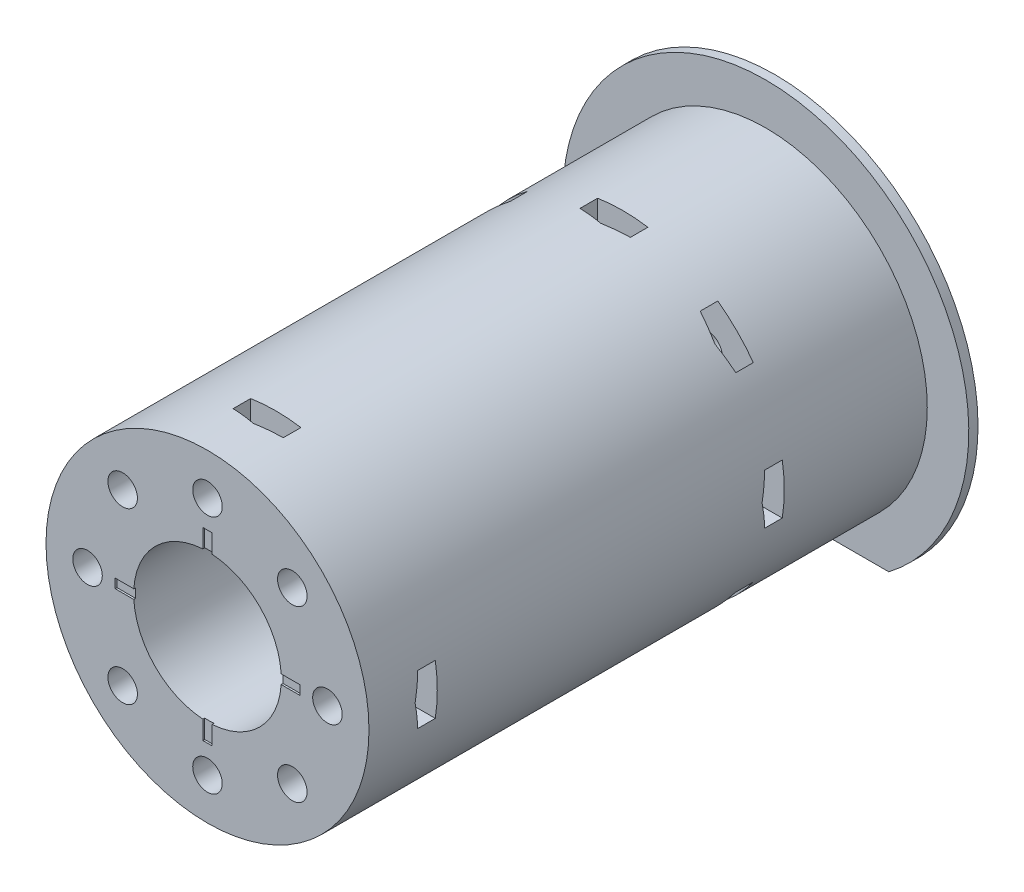
SolidWorks part; units mm, degrees
ref_plane "Front Plane" through (0, 0, 0) normal (1, 0, 0) x (0, 1, 0)
ref_plane "Top Plane" through (0, 0, 0) normal (0, 0, 1) x (0, 1, 0)
ref_plane "Right Plane" through (0, 0, 0) normal (0, 1, 0) x (-1, 0, 0)
sketch "Sketch1" plane through (0, 0, 0) normal (0, 0, 1) x (0, 1, 0)
  circle A0 centre (0, 0) radius 17.5
  dimension "D1" = 35
extrude "Boss-Extrude1" add sketch "Sketch1" along normal blind 60.5
sketch "Sketch3" plane through (0, 0, 0) normal (0, 0, -1) x (1, 0, 0)
  circle A0 centre (0, 0) radius 22
  dimension "D1" = 44
extrude "Boss-Extrude2" add sketch "Sketch3" along normal blind 1
sketch "Sketch2" plane through (0, 0, 60.5) normal (0, 0, 1) x (1, 0, 0)
  line L0 (-2.725, 15.725) -> (-2.725, 17.2865)
  line L2 (-2.725, 15.725) -> (-2.725, 10.275)
  line L3 (-2.725, 10.275) -> (2.725, 10.275)
  line L4 (2.725, 15.725) -> (2.725, 10.275)
  line L5 (-2.725, 15.725) -> (2.725, 10.275) construction
  line L6 (-2.725, 10.275) -> (2.725, 15.725) construction
  line L7 (2.725, 15.725) -> (2.725, 17.2865)
  circle A0 centre (0, 0) radius 13 construction
  circle A1 centre (0, 13) radius 1.6
  circle A2 centre (0, 0) radius 17.5 construction
  arc A3 (-2.725, 17.2865) -> (2.725, 17.2865) centre (0, 0) cw
  dimension "D1" = 26
  dimension "D4" = 3.2
  dimension "D2" = 5.45
  dimension "D3" = 5.45
extrude "Cut-Extrude1" cut sketch "Sketch2" against normal through all contours A1
extrude "Cut-Extrude2" cut sketch "Sketch2<4>" against normal blind 2.4 from offset 5 offset against normal yes
sketch "Sketch2<4>" plane through (0, 0, 60.5) normal (0, 0, 1) x (1, 0, 0) same geometry as "Sketch2"
extrude "Cut-Extrude3" cut sketch "Sketch2<5>" along normal blind 2.4 from offset 45 offset against normal yes
sketch "Sketch2<5>" plane through (0, 0, 60.5) normal (0, 0, 1) x (1, 0, 0) same geometry as "Sketch2"
chamfer "Chamfer1" distance 2.725 distance2 0.5 2 edges at (-2.725, 13.7808, 55.5) (2.725, 13.7808, 55.5) first distance on face at (1.6, 13, 55.5)
chamfer "Chamfer2" distance 2.725 distance2 0.5 2 edges at (-2.725, 13.7808, 17.9) (2.725, 13.7808, 17.9) first distance on face at (0, 13.8341, 17.9)
pattern_circular "CirPattern1" count 4 over 360 about axis through (0, 0, 60.5) along (0, 0, -1) of "Cut-Extrude2", "Chamfer1" reverse direction yes
pattern_circular "CirPattern3" count 8 over 360 about axis through (0, 0, 60.5) along (0, 0, -1) of "Cut-Extrude3", "Chamfer2", "Cut-Extrude1"
sketch "Sketch4" plane through (0, 0, -1) normal (0, 0, -1) x (1, 0, 0)
  circle A0 centre (0, 0) radius 8
  dimension "D1" = 16
extrude "Cut-Extrude4" cut sketch "Sketch4" against normal through all both and the other way through all
sketch "Sketch5" plane through (0, 0, -1) normal (0, 0, -1) x (1, 0, 0)
  line L0 (-0.5, -10) -> (-0.5, -0.5)
  line L1 (-10, 0.5) -> (-0.5, 0.5)
  line L2 (-10, 0.5) -> (-10, -0.5)
  line L3 (-10, -0.5) -> (-0.5, -0.5)
  line L4 (10, 0.5) -> (10, -0.5)
  line L5 (-10, 0.5) -> (10, -0.5) construction
  line L6 (-10, -0.5) -> (10, 0.5) construction
  line L7 (-0.5, -10) -> (0.5, -10)
  line L8 (0.5, -10) -> (0.5, -0.5)
  line L9 (-0.5, 10) -> (0.5, 10)
  line L10 (-0.5, -10) -> (0.5, 10) construction
  line L11 (0.5, -10) -> (-0.5, 10) construction
  line L14 (-0.5, 0.5) -> (-0.5, 10)
  line L15 (0.5, 0.5) -> (0.5, 10)
  line L16 (0.5, 0.5) -> (10, 0.5)
  line L19 (0.5, -0.5) -> (10, -0.5)
  point P0 (0, 0)
  point P6 (0, 0)
  dimension "D1" = 1
  dimension "D2" = 20
  dimension "D3" = 1
  dimension "D4" = 20
extrude "Cut-Extrude5" cut sketch "Sketch5" along normal blind 0.2 from surface starting at face at (-8, 0, 60.5)
sketch "Sketch6" plane through (0, 0, -1) normal (0, 0, -1) x (1, 0, 0)
  line L0 (0, 17.5) -> (-13.3323, 17.5)
  line L1 (0, 17.5) -> (13.3323, 17.5)
  circle A0 centre (0, 0) radius 17.5 construction
  circle A1 centre (0, 0) radius 17.5 construction
  circle A2 centre (0, 0) radius 22 construction
  arc A3 (13.3323, 17.5) -> (-13.3323, 17.5) centre (0, 0) ccw
extrude "Cut-Extrude6" cut sketch "Sketch6" against normal blind 1
